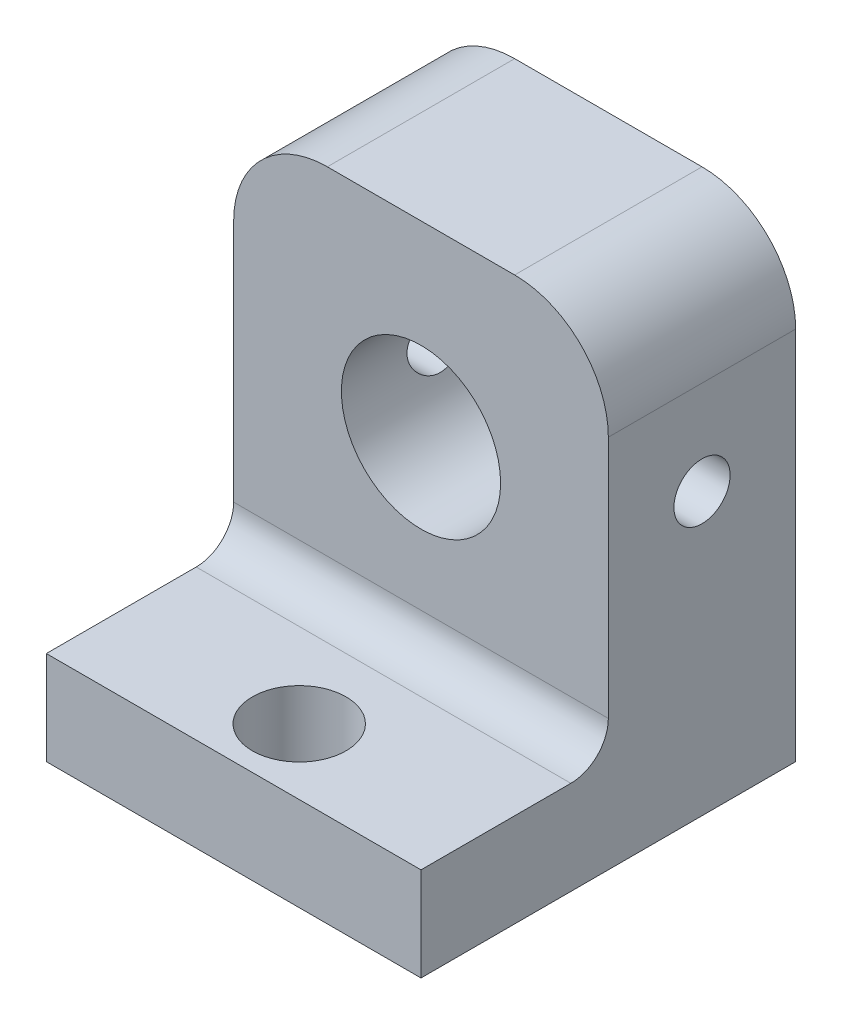
SolidWorks part; units mm, degrees
ref_plane "Front Plane" through (0, 0, 0) normal (0, 0, 1) x (1, 0, 0)
ref_plane "Top Plane" through (0, 0, 0) normal (0, 1, 0) x (1, 0, 0)
ref_plane "Right Plane" through (0, 0, 0) normal (1, 0, 0) x (0, 0, -1)
sketch "Sketch2" plane through (0, 0, 0) normal (0, 1, 0) x (1, 0, 0)
  line L0 (-10, 0) -> (10, 0)
  line L1 (10, -10) -> (-10, -10)
  line L2 (10, -10) -> (10, 10)
  line L3 (10, 10) -> (-10, 10)
  line L4 (-10, -10) -> (-10, 10)
  line L5 (10, -10) -> (-10, 10) construction
  line L6 (10, 10) -> (-10, -10) construction
  circle A0 centre (0, -6.5) radius 2.5
  point P0 (0, 0)
  dimension "D1" = 5
  dimension "D2" = 20
  dimension "D3" = 20
  dimension "D4" = 3.5
extrude "Boss-Extrude1" add sketch "Sketch2" along normal blind 5 contours L4 L1 L2 L0 A0 | L4 L0 L2 L3 region at (0, 0, -5) region at (0, 0, 0.2236)
extrude "Boss-Extrude2" add sketch "Sketch2<3>" along normal blind 25 contours L4 L0 L2 L3 region at (0, 0, -5)
sketch "Sketch2<3>" plane through (0, 0, 0) normal (0, 1, 0) x (1, 0, 0) same geometry as "Sketch2"
sketch "Sketch4" plane through (0, 0, 0) normal (0, 0, 1) x (1, 0, 0)
  line L0 (-10, 25) -> (10, 25) construction
  line L1 (10, 25) -> (10, 5) construction
  circle A0 centre (0, 15) radius 4.25
  dimension "D1" = 8.5
  dimension "D2" = 10
  dimension "D3" = 10
extrude "Cut-Extrude1" cut sketch "Sketch4" against normal blind 88
sketch "Sketch5" plane through (10, 0, 0) normal (1, 0, 0) x (0, 0, -1)
  line L0 (0, 25) -> (10, 25) construction
  line L1 (0, 25) -> (0, 5) construction
  circle A0 centre (5, 15) radius 1.5
  dimension "D1" = 3
  dimension "D2" = 10
  dimension "D3" = 5
extrude "Cut-Extrude2" cut sketch "Sketch5" against normal blind 88
fillet "Fillet1" radius 5 2 edges at (-10, 25, -5) (10, 25, -5)
fillet "Fillet2" radius 2 1 edges at (0, 5, 0)
